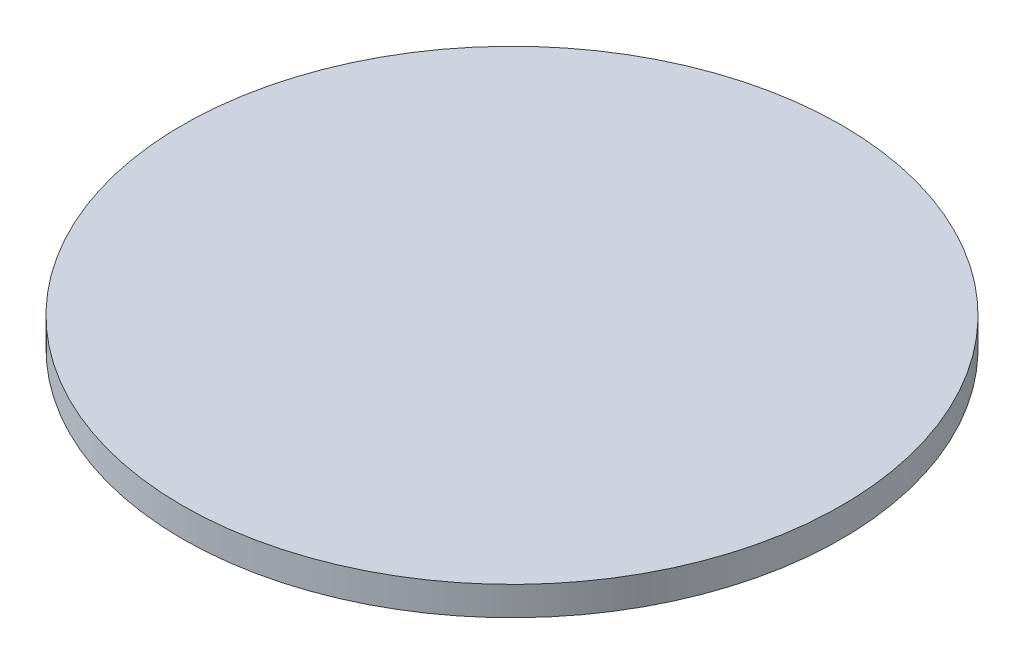
SolidWorks part; units mm, degrees
material "ABS"
ref_plane "Front Plane" through (0, 0, 0) normal (0, 0, 1) x (1, 0, 0)
ref_plane "Top Plane" through (0, 0, 0) normal (0, 1, 0) x (1, 0, 0)
ref_plane "Right Plane" through (0, 0, 0) normal (1, 0, 0) x (0, 0, -1)
sketch "Sketch1" plane through (0, 0, 0) normal (0, 0, 1) x (1, 0, 0)
  line L0 (0, 0) -> (68.5, 0)
  line L1 (68.5, 0) -> (68.5, -6)
  line L2 (68.5, -6) -> (66.5, -6)
  line L3 (66.5, -6) -> (66.5, -3)
  line L5 (53.5, -3) -> (53.5, -6)
  line L6 (53.5, -6) -> (50.5, -6)
  line L7 (50.5, -6) -> (50.5, -3)
  line L8 (50.5, -3) -> (6, -3)
  line L9 (6, -3) -> (6, -5)
  line L10 (6, -5) -> (0, -5)
  line L11 (0, -5) -> (0, 0)
  line L12 (62.3516, -3) -> (66.5, -3)
  line L13 (57.6484, -3) -> (53.5, -3)
  arc A0 (62.3516, -3) -> (57.6484, -3) centre (60, -6.6) ccw
  point P4 (67.5, -6)
  point P9 (0, 0)
  dimension "D2" = 4.3
  dimension "D1" = 60
  dimension "D3" = 6.5
  dimension "D4" = 3
  dimension "D5" = 6.5
  dimension "D6" = 3
  dimension "D7" = 2
  dimension "D8" = 50.5
  dimension "D9" = 0.6
  dimension "D10" = 5
  dimension "D11" = 6
revolve "Revolve1" add sketch "Sketch1" angle 360 about L11
